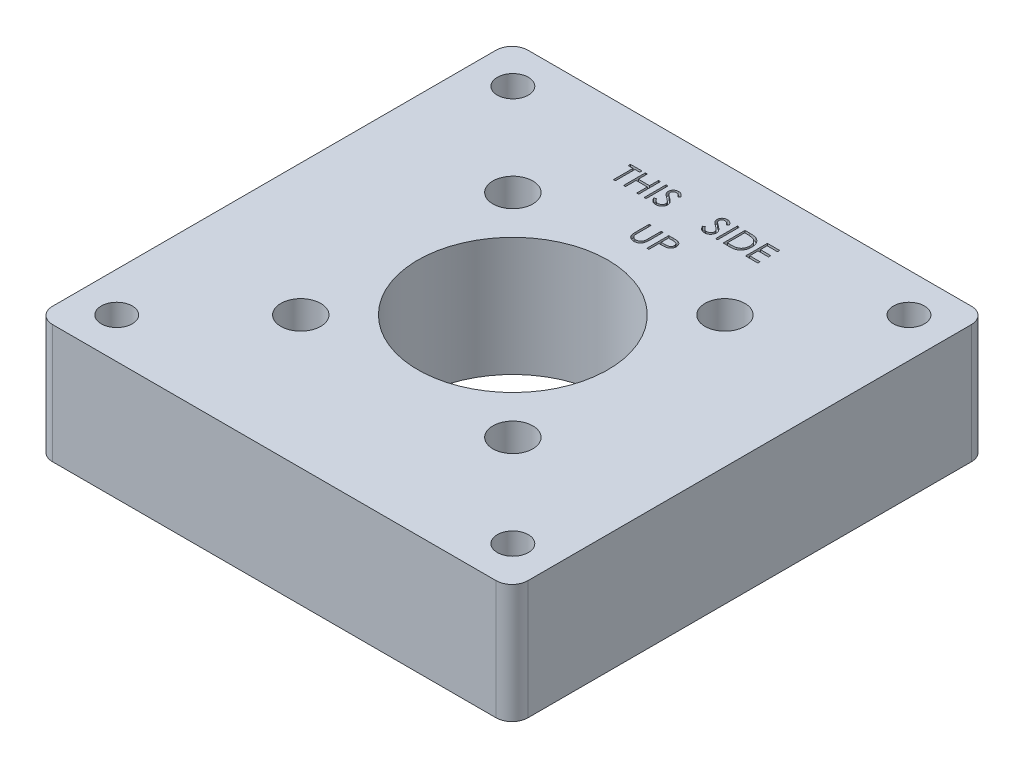
SolidWorks part; units mm, degrees
material "ABS PC"
ref_plane "Front Plane" through (0, 0, 0) normal (0, 0, 1) x (1, 0, 0)
ref_plane "Top Plane" through (0, 0, 0) normal (0, 1, 0) x (1, 0, 0)
ref_plane "Right Plane" through (0, 0, 0) normal (1, 0, 0) x (0, 0, -1)
sketch "Sketch1" plane through (0, 0, 0) normal (0, 1, 0) x (1, 0, 0)
  line L0 (3.1695, 50.4318) -> (3.1695, 88.3951) construction
  line L1 (3.1695, 88.3951) -> (41.2695, 88.3951)
  line L2 (41.2695, 88.3951) -> (41.2695, 12.1951)
  line L3 (41.2695, 12.1951) -> (-34.9305, 12.1951)
  line L4 (-34.9305, 12.1951) -> (-34.9305, 88.3951)
  line L5 (-34.9305, 88.3951) -> (3.1695, 88.3951)
  circle A1 centre (3.1695, 50.4318) radius 15.24
  point P7 (0, 0)
  dimension "D1" = 76.2
  dimension "D3" = 30.48
  dimension "D2" = 76.2
  dimension "D4" = 37.9633
extrude "Boss-Extrude2" add sketch "Sketch1" along normal blind 19.05
sketch "Sketch3" plane through (0, 19.05, 0) normal (0, 1, 0) x (1, 0, 0)
  circle A4 centre (20.1695, 33.4318) radius 3.2
  circle A5 centre (-13.8305, 33.4318) radius 3.2
  circle A6 centre (20.1695, 67.4318) radius 3.2
  circle A7 centre (-13.8305, 67.4318) radius 3.2
extrude "Cut-Extrude2" cut sketch "Sketch3" against normal blind 17.145
hole_wizard "Ø3.2 (3.2) Diameter Hole2" positions "Sketch6" profile "Sketch5" hole size "Ø3.2" standard "ANSI Metric" end condition through all
sketch "Sketch6" plane through (0, 1.905, 0) normal (0, 1, 0) x (1, 0, 0)
  point P12 (-13.8305, 67.4318)
  point P15 (20.1695, 67.4318)
  point P18 (20.1695, 33.4318)
  point P21 (-13.8305, 33.4318)
sketch "Sketch5" plane through (-13.8305, 1.905, -67.4318) normal (1, 0, 0) x (0, 0, 1)
  line L0 (0, 0) -> (0, 1.905)
  line L1 (0, 1.905) -> (1.6, 1.905)
  line L2 (1.6, 1.905) -> (1.6, 1.4)
  line L3 (1.6, 1.4) -> (3, 0)
  line L5 (3, 0) -> (0, 0)
  line L6 (-1.6, 1.4) -> (-3, 0) construction
  line L11 (0, -6.35) -> (0, 107.95) construction
  dimension "Thru Hole Dia." = 3.2
  dimension "Thru Hole Depth" = 1.905
  dimension "Near C'Sink Dia." = 6
  dimension "Near C'Sink Angle" = 90
sketch "Sketch7" plane through (0, 19.05, 0) normal (0, 1, 0) x (1, 0, 0)
  line L8 (3.1695, 50.4318) -> (34.9195, 50.4318) construction
  line L9 (34.9195, 50.4318) -> (34.9195, 82.1818) construction
  line L10 (34.9195, 82.1818) -> (-28.5805, 82.1818) construction
  line L11 (-28.5805, 82.1818) -> (-28.5805, 18.6818) construction
  line L12 (-28.5805, 18.6818) -> (34.9195, 18.6818) construction
  line L13 (34.9195, 18.6818) -> (34.9195, 50.4318) construction
  dimension "D1" = 31.75
  dimension "D5" = 31.75
  dimension "D6" = 63.5
  dimension "D7" = 63.5
  dimension "D8" = 63.5
hole_wizard "#10 Clearance Hole1" positions "Sketch8" profile "Sketch9" hole size "#10" standard "ANSI Inch" end condition through all
sketch "Sketch8" plane through (0, 19.05, 0) normal (0, 1, 0) x (1, 0, 0)
  point P0 (34.9195, 82.1818)
  point P3 (-28.5805, 82.1818)
  point P6 (-28.5805, 18.6818)
  point P9 (34.9195, 18.6818)
  point P12 (28.5695, 75.8318)
  point P14 (28.5695, 25.0318)
  point P16 (-22.2305, 25.0318)
  point P18 (-22.2305, 75.8318)
sketch "Sketch9" plane through (34.9195, 19.05, -82.1818) normal (1, 0, 0) x (0, 0, 1)
  line L0 (0, 0) -> (0, 19.05)
  line L1 (0, 19.05) -> (2.4892, 19.05)
  line L2 (2.4892, 19.05) -> (2.4892, 0)
  line L5 (2.4892, 0) -> (0, 0)
  line L11 (0, -6.35) -> (0, 107.95) construction
  dimension "Thru Hole Dia." = 4.9784
  dimension "Thru Hole Depth" = 19.05
sketch "Sketch10" plane through (0, 19.05, 0) normal (0, 1, 0) x (1, 0, 0)
  text T0 "THIS    SIDE\r\n       UP"
extrude "Cut-Extrude1" cut sketch "Sketch10" against normal blind 0.635
fillet "Fillet2" radius 2.54 4 edges at (-34.9305, 9.525, -12.1951) (41.2695, 9.525, -12.1951) (41.2695, 9.525, -88.3951) (-34.9305, 9.525, -88.3951)
